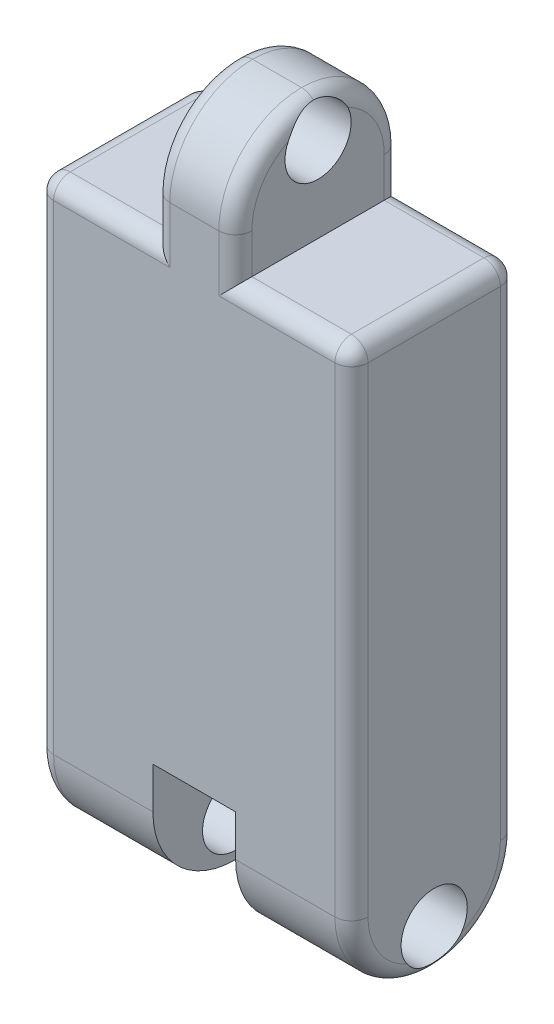
SolidWorks part; units mm, degrees
material "Cast Alloy Steel"
ref_plane "Front Plane" through (0, 0, 0) normal (0, 0, 1) x (1, 0, 0)
ref_plane "Top Plane" through (0, 0, 0) normal (0, 1, 0) x (1, 0, 0)
ref_plane "Right Plane" through (0, 0, 0) normal (1, 0, 0) x (0, 0, -1)
sketch "Sketch1" plane through (0, 0, 0) normal (0, 0, 1) x (1, 0, 0)
  line L0 (-24.8, 175) -> (-24.8, 249)
  line L1 (-95, 175) -> (-24.8, 175)
  line L2 (-95, 175) -> (-95, -175)
  line L3 (-95, -175) -> (95, -175)
  line L4 (95, 175) -> (95, -175)
  line L5 (-95, 175) -> (95, -175) construction
  line L6 (-95, -175) -> (95, 175) construction
  line L9 (-24.8, 249) -> (24.8, 249)
  line L11 (24.8, 175) -> (95, 175)
  line L14 (24.8, 175) -> (24.8, 249)
  point P0 (0, 0)
  point P6 (0, 100)
  point P8 (0, 249)
  dimension "D1" = 350
  dimension "D2" = 190
  dimension "D3" = 74
  dimension "D4" = 49.6
extrude "Boss-Extrude1" add sketch "Sketch1" against normal blind 100
sketch "Sketch2" plane through (0, 0, 0) normal (0, 0, 1) x (1, 0, 0)
  line L0 (-95, -175) -> (95, -175) construction
  line L1 (-25, -200) -> (25, -200)
  line L2 (-25, -200) -> (-25, -150)
  line L3 (-25, -150) -> (25, -150)
  line L4 (25, -200) -> (25, -150)
  line L5 (-25, -200) -> (25, -150) construction
  line L6 (-25, -150) -> (25, -200) construction
  point P0 (0, -175)
  dimension "D1" = 50
  dimension "D2" = 50
extrude "Cut-Extrude1" cut sketch "Sketch2" against normal through all
fillet "Fillet1" radius 50 2 edges at (0, 249, -100) (0, 249, 0)
sketch "Sketch6" plane through (0, 0, 0) normal (1, 0, 0) x (0, 0, -1)
  line L0 (100, -150) -> (0, -150) construction
  line L1 (100, -150) -> (0, -150)
  arc A0 (100, -150) -> (0, -150) centre (50, -150) ccw
extrude "Cut-Extrude2" cut sketch "Sketch6" along normal mid plane 50
sketch "Sketch7" plane through (-95, 0, 0) normal (-1, 0, 0) x (0, 0, 1)
  line L0 (-100, -175) -> (0, -175) construction
  circle A0 centre (-50, -150) radius 20
  point P4 (-50, -175)
  dimension "D2" = 40
  dimension "D1" = 25
extrude "Cut-Extrude3" cut sketch "Sketch7" against normal through all
fillet "Fillet2" radius 50 2 edges at (-60, -175, -100) (-60, -175, 0)
sketch "Sketch9" plane through (0, 0, 0) normal (0, 0, 1) x (1, 0, 0)
  line L0 (-25, -137.5) -> (-25, -125)
  line L1 (-95, -125) -> (95, -125) construction
  line L2 (-25, -125) -> (25, -125)
  line L3 (25, -125) -> (25, -137.5)
  line L4 (25, -137.5) -> (-25, -137.5)
extrude "Cut-Extrude6" cut sketch "Sketch9" against normal through all
sketch "Sketch10" plane through (0, 0, 0) normal (1, 0, 0) x (0, 0, -1)
  line L0 (0, -125) -> (100, -125)
  arc A0 (100, -125) -> (0, -125) centre (50, -211.6696) ccw
extrude "Cut-Extrude7" cut sketch "Sketch10" against normal mid plane 50
sketch "Sketch11" plane through (0, 0, 0) normal (0, 0, 1) x (1, 0, 0)
  line L0 (-25, -125) -> (-25, -100)
  line L1 (-25, -100) -> (25, -100)
  line L2 (25, -100) -> (25, -125)
  line L3 (25, -125) -> (-25, -125)
  dimension "D1" = 25
fillet "Fillet3" radius 10 20 edges at (24.8, 187, -100) (24.8, 234.3553, -85.3553) (24.8, 187, 0) (-24.8, 187, 0) (-24.8, 187, -100) (-24.8, 234.3553, -85.3553) (95, 25, -100) (95, -160.3553, -85.3553) (95, -160.3553, -14.6447) (-95, 25, -100) (-95, -160.3553, -85.3553) (-95, -160.3553, -14.6447) (59.9, 175, 0) (59.9, 175, -100) (-59.9, 175, -100) (-59.9, 175, 0) (24.8, 234.3553, -14.6447) (-24.8, 234.3553, -14.6447) (95, 25, 0) (-95, 25, 0)
extrude "Cut-Extrude8" cut sketch "Sketch11" against normal blind 99
sketch "Sketch13" plane through (0, 0, -100) normal (0, 0, -1) x (-1, 0, 0)
  line L0 (-25, -125) -> (-25, -155)
  line L1 (-25, -155) -> (25.0188, -155)
  line L2 (25.0188, -155) -> (25, -125)
  line L3 (25, -125) -> (-25, -125)
  dimension "D1" = 30
extrude "Boss-Extrude7" add sketch "Sketch13" along normal blind 0.1 separate body
fillet "Fillet4" radius 10 3 edges at (-25.0094, -140, -100.1) (25, -140, -100.1) (-0.0094, -155, -100.1)
fillet "Fillet5" radius 10 6 edges at (92.0711, 172.0711, -97.0711) (92.0711, 172.0711, -2.9289) (-92.0711, 172.0711, -97.0711) (-92.0711, 172.0711, -2.9289) (95, 175, -50) (-95, 175, -50)
sketch "Sketch14" plane through (24.8, 0, 0) normal (1, 0, 0) x (0, 0, -1)
  line L0 (90, 175) -> (10, 175) construction
  circle A0 centre (50, 226) radius 20
  dimension "D1" = 40
  dimension "D2" = 23
  dimension "D3" = 51
extrude "Cut-Extrude9" cut sketch "Sketch14" against normal through all
